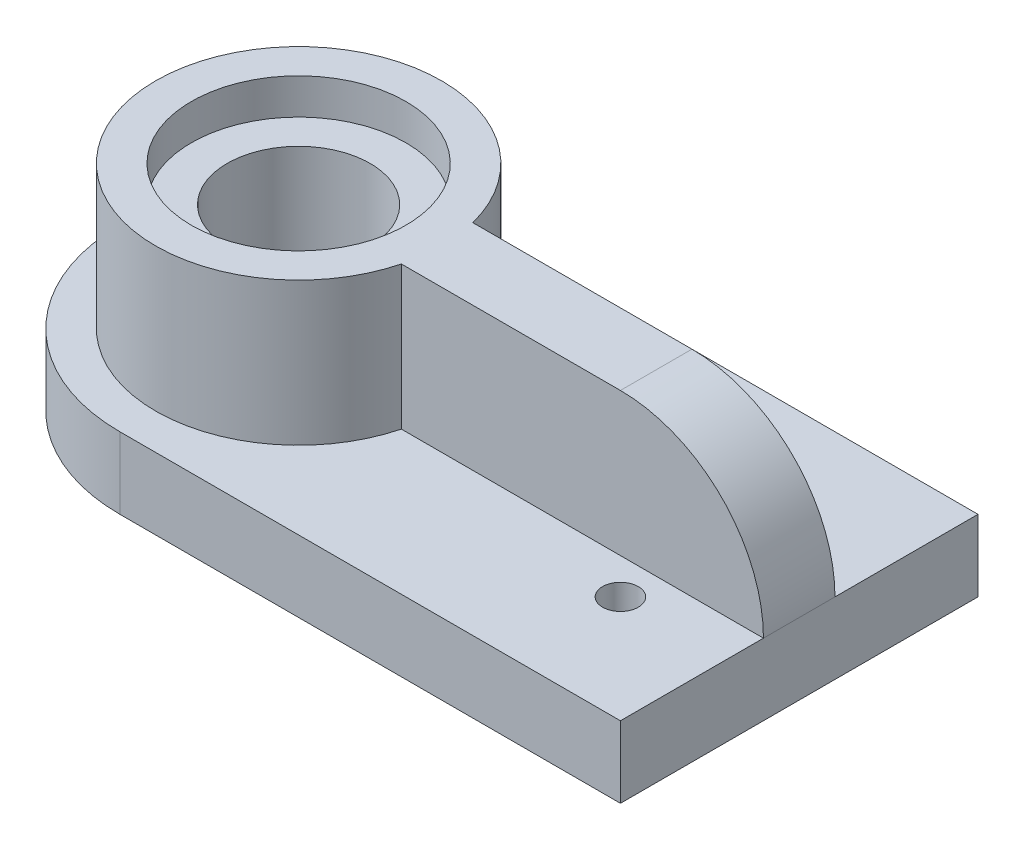
SolidWorks part; units mm, degrees
ref_plane "Front Plane" through (0, 0, 0) normal (0, 0, 1) x (1, 0, 0)
ref_plane "Top Plane" through (0, 0, 0) normal (0, 1, 0) x (1, 0, 0)
ref_plane "Right Plane" through (0, 0, 0) normal (1, 0, 0) x (0, 0, -1)
sketch "Sketch10" plane through (0, 0, 0) normal (0, 1, 0) x (1, 0, 0)
  line L0 (44.3649, 30) -> (95, 30)
  line L1 (0, 0) -> (95, 0)
  line L2 (0, 0) -> (0, 50)
  line L3 (0, 50) -> (95, 50)
  line L4 (95, 0) -> (95, 50)
  line L5 (95, 30) -> (95, 20)
  line L6 (95, 20) -> (44.3649, 20)
  arc A0 (44.3649, 30) -> (44.3649, 20) centre (25, 25) ccw
  circle A1 centre (25, 25) radius 10
  circle A2 centre (25, 25) radius 15
  circle A3 centre (80, 35) radius 2.5
  circle A4 centre (80, 15) radius 2.5
  point P17 (0, 0)
  dimension "D1" = 95
  dimension "D5" = 5
  dimension "D6" = 5
  dimension "D7" = 15
  dimension "D8" = 15
  dimension "D9" = 15
  dimension "D11" = 40
  dimension "D12" = 30
  dimension "D13" = 20
  dimension "D2" = 50
  dimension "D3" = 20
  dimension "D4" = 10
  dimension "D10" = 70
  dimension "D14" = 25
extrude "Boss-Extrude3" add sketch "Sketch10" along normal blind 10 contours A0 L0 L4 L3 L2 L1 L6 A4 A3 region at (3.9265, 0, -25)
extrude "Boss-Extrude4" add sketch "Sketch10<3>" along normal blind 30 contours L0 A0 L6 L4 A2 | A2 A1 region at (46.4298, 0, -25) region at (10.4243, 0, -25)
sketch "Sketch10<3>" plane through (0, 0, 0) normal (0, 1, 0) x (1, 0, 0) same geometry as "Sketch10"
fillet "Fillet1" 2 edges at (0, 5, 0) (0, 5, -50) type full round first side face at (47.5, 5, 0) second side face at (47.5, 5, -50) middle face at (0, 5, -25)
fillet "Fillet2" radius 20 1 edges at (95, 30, -25)
extrude "Cut-Extrude1" cut sketch "Sketch10<6>" against normal blind 5 from surface contours A2 A1 region at (10.4243, 0, -25) starting at face at (49.8412, 30, -25)
sketch "Sketch10<6>" plane through (0, 0, 0) normal (0, 1, 0) x (1, 0, 0) same geometry as "Sketch10"
